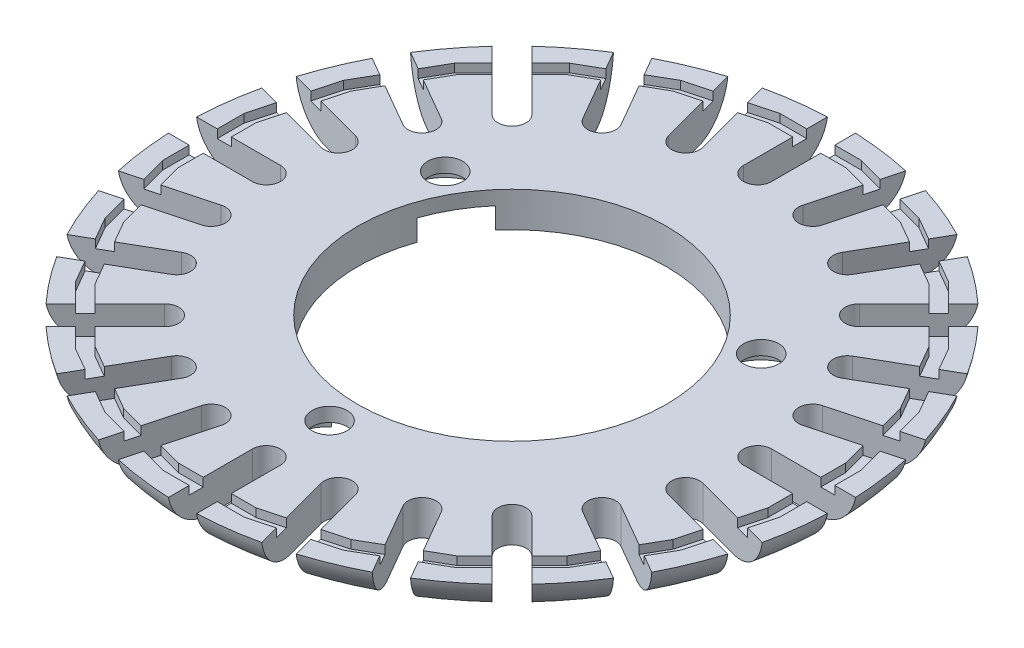
SolidWorks part; units mm, degrees
ref_plane "Plano frontal" through (0, 0, 0) normal (0, 0, 1) x (1, 0, 0)
ref_plane "Plano superior" through (0, 0, 0) normal (0, 1, 0) x (1, 0, 0)
ref_plane "Plano direito" through (0, 0, 0) normal (1, 0, 0) x (0, 0, -1)
sketch "Esboço1" plane through (0, 0, 0) normal (0, 1, 0) x (1, 0, 0)
  circle A0 centre (0, 0) radius 23.5
  dimension "D1" = 47
extrude "Ressalto-extrusão1" add sketch "Esboço1" along normal blind 2.5
fillet "Filete1" radius 3 1 edges at (0, 0, 23.5)
sketch "Esboço2" plane through (0, 2.5, 0) normal (0, 1, 0) x (1, 0, 0)
  line L0 (0, 0) -> (0, 23.9078) construction
  line L2 (1, 17.5) -> (1, 23.5)
  line L3 (1, 23.5) -> (-1, 23.5)
  line L4 (0, 23.5) -> (7.8408, 23.5) construction
  line L5 (-1, 17.5) -> (-1, 23.5)
  arc A0 (-1, 17.5) -> (1, 17.5) centre (0, 17.5) ccw
  circle A3 centre (0, 0) radius 23.5 construction
  point P12 (0, 16.5)
  dimension "D2" = 6
  dimension "D1" = 1
extrude "Corte-extrusão1" cut sketch "Esboço2" against normal through all
pattern_circular "PadrãoCircular1" count 24 over 360 about axis through (0, 2.5, 0) along (0, 1, 0) of "Corte-extrusão1"
sketch "Esboço4" plane through (0, 2.5, 0) normal (0, 1, 0) x (1, 0, 0)
  line L0 (0, 0) -> (-3.0674, 23.299) construction
  line L1 (0, 0) -> (3.0674, 23.299) construction
  line L2 (-2.8964, 22) -> (2.8964, 22)
  line L3 (2.8964, 22) -> (2.7647, 21)
  line L4 (2.7647, 21) -> (-2.7647, 21)
  line L5 (-2.7647, 21) -> (-2.8964, 22)
  arc A2 (5.1108, 22.9375) -> (1, 23.4787) centre (0, 0) ccw construction
  arc A3 (-1, 23.4787) -> (-5.1108, 22.9375) centre (0, 0) ccw construction
  dimension "D1" = 1
  dimension "D2" = 21
extrude "Corte-extrusão2" cut sketch "Esboço4" against normal blind 0.6
pattern_circular "PadrãoCircular2" count 24 over 360 about axis through (0, 2.5, 0) along (0, 1, 0) of "Corte-extrusão2"
sketch "Esboço5" plane through (0, 2.5, 0) normal (0, 1, 0) x (1, 0, 0)
  circle A0 centre (0, 0) radius 11
  dimension "D1" = 22
extrude "Corte-extrusão3" cut sketch "Esboço5" against normal through all
sketch "Esboço6" plane through (0, 2.5, 0) normal (0, 1, 0) x (1, 0, 0)
  circle A4 centre (-11.2583, 6.5) radius 1.25
  circle A5 centre (11.2583, 6.5) radius 1.25
  circle A6 centre (0, -13) radius 1.25
  dimension "D5" = 2.5
extrude "Corte-extrusão5" cut sketch "Esboço6" against normal blind 2.5
sketch "Esboço8" plane through (0, 0, 0) normal (0, -1, 0) x (-1, 0, 0)
  circle A0 centre (11.2583, 6.5) radius 3
  circle A1 centre (-11.2583, 6.5) radius 3
  circle A2 centre (0, -13) radius 3
  dimension "D1" = 6
extrude "Corte-extrusão6" cut sketch "Esboço8" against normal blind 1.5
